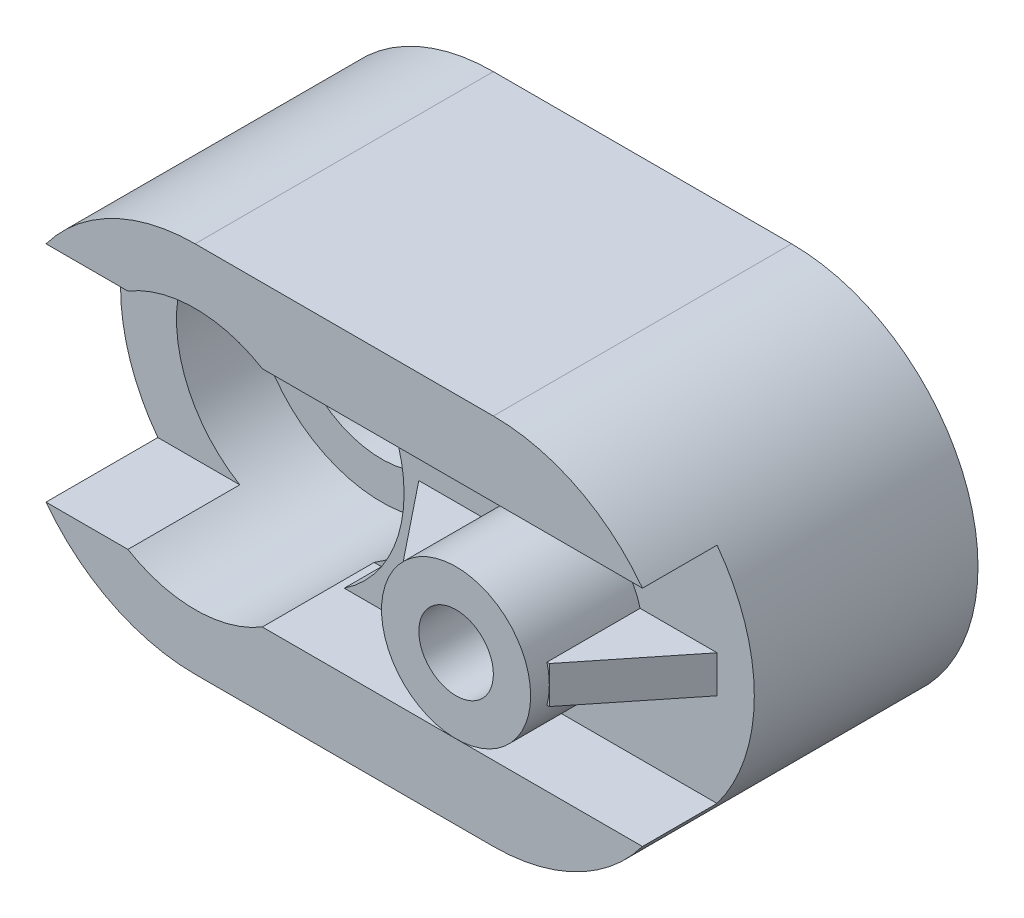
SolidWorks part; units mm, degrees
ref_plane "Front Plane" through (0, 0, 0) normal (0, 0, 1) x (1, 0, 0)
ref_plane "Top Plane" through (0, 0, 0) normal (0, 1, 0) x (1, 0, 0)
ref_plane "Right Plane" through (0, 0, 0) normal (1, 0, 0) x (0, 0, -1)
sketch "Sketch1" plane through (0, 0, 0) normal (0, 0, 1) x (1, 0, 0)
  line L1 (0, 0) -> (180, 0)
  line L2 (0, 0) -> (0, 100)
  line L3 (0, 100) -> (180, 100)
  line L4 (180, 0) -> (180, 100)
  arc A0 (50, 100) -> (50, 0) centre (50, 50) ccw
  arc A1 (130, 100) -> (130, 0) centre (130, 50) cw
  dimension "D7" = 50
  dimension "D10" = 50
  dimension "D1" = 180
  dimension "D2" = 100
  dimension "D3" = 50
  dimension "D4" = 50
  dimension "D5" = 50
  dimension "D6" = 50
  dimension "D8" = 50
  dimension "D9" = 50
extrude "Boss-Extrude1" add sketch "Sketch1" along normal blind 80 contours A1 L3 A0 L1 region at (90, 50, 0)
sketch "Sketch2" plane through (0, 0, 0) normal (1, 0, 0) x (0, 0, -1)
  line L0 (-80, 100) -> (-80, 0) construction
  line L1 (-80, 80) -> (-60, 80)
  line L2 (-80, 80) -> (-80, 70)
  line L3 (-80, 70) -> (-60, 70)
  line L4 (-60, 80) -> (-60, 70)
  line L5 (-80, 100) -> (0, 100) construction
  line L6 (-80, 0) -> (0, 0) construction
  line L7 (-80, 30) -> (-60, 30)
  line L8 (-80, 30) -> (-80, 20)
  line L9 (-80, 20) -> (-60, 20)
  line L10 (-60, 30) -> (-60, 20)
  dimension "D1" = 20
  dimension "D2" = 10
  dimension "D3" = 20
  dimension "D4" = 10
  dimension "D5" = 20
  dimension "D6" = 20
extrude "Cut-Extrude1" cut sketch "Sketch2" along normal blind 209
sketch "Sketch3" plane through (0, 0, 80) normal (0, 0, 1) x (1, 0, 0)
  line L0 (50, 0) -> (130, 0) construction
  circle A0 centre (130, 50) radius 10
  arc A1 (175.8258, 30) -> (175.8258, 70) centre (130, 50) ccw construction
  point P2 (180, 50)
  dimension "D1" = 20
  dimension "D2" = 50
  dimension "D3" = 50
extrude "Cut-Extrude2" cut sketch "Sketch3" against normal blind 40
sketch "Sketch4" plane through (0, 0, 80) normal (0, 0, 1) x (1, 0, 0)
  circle A0 centre (130, 50) radius 10
  circle A1 centre (130, 50) radius 20
  dimension "D1" = 20
  dimension "D2" = 40
extrude "Boss-Extrude2" add sketch "Sketch4" along normal blind 10
sketch "Sketch7" plane through (0, 0, 90) normal (0, 0, 1) x (1, 0, 0)
  point P0 (130, 50)
hole_wizard "Ø20.0mm Dowel Hole1" positions "3DSketch3" profile "Sketch8" hole size "Ø20.0" standard "ISO"
sketch3d "3DSketch3"
  point P0 (130, 50, 90)
sketch "Sketch8" plane through (130, 50, 90) normal (1, 0, 0) x (0, -1, 0)
  line L0 (0, 0) -> (0, 56.0086)
  line L1 (0, 56.0086) -> (10, 50)
  line L2 (10, 50) -> (10, 0)
  line L5 (10, 0) -> (0, 0)
  line L10 (0, 56.0086) -> (-10, 50) construction
  line L11 (0, -6.35) -> (0, 107.95) construction
  dimension "Hole Dia." = 20
  dimension "Hole Depth" = 50
  dimension "Drill Angle" = 118
sketch "Sketch9" plane through (0, 0, 80) normal (0, 0, 1) x (1, 0, 0)
  line L0 (4.1742, 30) -> (130, 30) construction
  line L1 (130, 70) -> (4.1742, 70)
  line L2 (130, 30) -> (4.1742, 30)
  arc A0 (130, 70) -> (130, 30) centre (130, 50) ccw
  arc A1 (4.1742, 70) -> (4.1742, 30) centre (50, 50) ccw
  arc A2 (4.1742, 70) -> (4.1742, 30) centre (50, 50) ccw construction
extrude "Cut-Extrude3" cut sketch "Sketch9" against normal blind 20
sketch "Sketch10" plane through (0, 0, 60) normal (0, 0, 1) x (1, 0, 0)
  line L0 (50, 0) -> (130, 0) construction
  circle A0 centre (50, 50) radius 10
  arc A1 (50, 100) -> (50, 0) centre (50, 50) ccw construction
  point P4 (0, 50)
  dimension "D1" = 20
  dimension "D2" = 50
  dimension "D3" = 50
extrude "Cut-Extrude4" cut sketch "Sketch10" against normal blind 74
sketch "Sketch11" plane through (0, 0, 60) normal (0, 0, 1) x (1, 0, 0)
  circle A0 centre (50, 50) radius 10
  circle A1 centre (50, 50) radius 25
  dimension "D1" = 20
  dimension "D2" = 50
extrude "Cut-Extrude5" cut sketch "Sketch11" against normal blind 40
sketch "Sketch12" plane through (0, 0, 60) normal (0, 0, 1) x (1, 0, 0)
  line L0 (170, 20) -> (10, 20) construction
  line L1 (10, 80) -> (70, 80)
  line L2 (170, 80) -> (10, 80) construction
  line L3 (10, 20) -> (70, 20)
  arc A0 (10, 80) -> (10, 20) centre (50, 50) ccw
  arc A1 (70, 80) -> (70, 20) centre (50, 50) cw
  circle M1 centre (50, 50) radius 25
  line M2 (170, 80) -> (10, 80)
  arc M3 (10, 80) -> (10, 20) centre (50, 50) ccw
  line M4 (10, 20) -> (170, 20)
  dimension "D1" = 60
  dimension "D2" = 60
extrude "Cut-Extrude6" cut sketch "Sketch12" against normal blind 10 contours A1 M2 M3 M4 M1 region at (40, 78.9509, 60)
sketch "Sketch14" plane through (0, 0, 60) normal (0, 0, 1) x (1, 0, 0)
  circle A0 centre (50, 50) radius 35
  circle A1 centre (50, 50) radius 25
  dimension "D1" = 70
  dimension "D2" = 50
extrude "Cut-Extrude7" cut sketch "Sketch14" against normal blind 30
sketch "Sketch15" plane through (0, 0, 80) normal (0, 0, 1) x (1, 0, 0)
  circle A0 centre (50, 50) radius 35
  dimension "D1" = 70
extrude "Cut-Extrude8" cut sketch "Sketch15" against normal blind 30
sketch "Sketch16" plane through (0, 0, 80) normal (0, 0, 1) x (1, 0, 0)
  line L0 (130, 70) -> (175.8258, 70)
  line L1 (130, 30) -> (175.8258, 30)
  arc A0 (130, 70) -> (130, 30) centre (130, 50) cw
  arc A1 (175.8258, 70) -> (175.8258, 30) centre (130, 50) cw
  arc A2 (175.8258, 30) -> (175.8258, 70) centre (130, 50) ccw construction
extrude "Cut-Extrude9" cut sketch "Sketch16" against normal blind 20
sketch "Sketch17" plane through (0, 0, 60) normal (0, 0, 1) x (1, 0, 0)
  line L1 (110, 50) -> (90, 50)
  line L2 (110, 50) -> (110, 45)
  line L3 (110, 45) -> (90, 45)
  line L4 (90, 50) -> (90, 45)
  line L5 (150, 50) -> (170, 50)
  line L6 (150, 50) -> (150, 45)
  line L7 (150, 45) -> (170, 45)
  line L8 (170, 50) -> (170, 45)
  line L9 (50, 0) -> (130, 0) construction
  line L10 (110, 45) -> (110.6351, 45)
  line L11 (150, 45) -> (149.3649, 45)
  circle A0 centre (130, 50) radius 20 construction
  arc A1 (110, 50) -> (110.6351, 45) centre (130, 50) ccw
  arc A2 (150, 50) -> (149.3649, 45) centre (130, 50) cw
  circle M1 centre (130, 50) radius 20
  dimension "D1" = 20
  dimension "D2" = 5
  dimension "D3" = 5
  dimension "D4" = 20
  dimension "D5" = 45
  dimension "D6" = 45
extrude "Boss-Extrude3" add sketch "Sketch17" along normal blind 25 contours L11 L6 M1 | L8 L5 L6 L7 | L2 L10 M1 | L1 L4 L3 L2 region at (100, 47.5, 60) region at (110.19, 46.246, 60) region at (160, 47.5, 60) region at (149.81, 46.246, 60)
sketch "Sketch18" plane through (0, 0, 85) normal (0, 0, 1) x (1, 0, 0)
  line L0 (110, 55) -> (110.6351, 55)
  line L1 (90, 50) -> (110, 50)
  line L2 (90, 50) -> (90, 55)
  line L3 (90, 55) -> (110, 55)
  line L4 (110, 50) -> (110, 55)
  circle A0 centre (130, 50) radius 20 construction
  arc A1 (110.6351, 55) -> (110, 50) centre (130, 50) ccw
  line M2 (110, 50) -> (90, 50)
  dimension "D1" = 5
  dimension "D2" = 20
extrude "Boss-Extrude4" add sketch "Sketch18" against normal blind 25 contours A1 L0 L4 | L4 L3 L2 M2 region at (100, 52.5, 85) region at (110.19, 53.754, 85)
sketch "Sketch19" plane through (0, 0, 85) normal (0, 0, 1) x (1, 0, 0)
  line L0 (150, 55) -> (149.3649, 55)
  line L1 (170, 50) -> (150, 50)
  line L2 (170, 50) -> (170, 55)
  line L3 (170, 55) -> (150, 55)
  line L4 (150, 50) -> (150, 55)
  circle A0 centre (130, 50) radius 20 construction
  arc A1 (149.3649, 55) -> (150, 50) centre (130, 50) cw
  line M3 (170, 50) -> (150, 50)
  dimension "D1" = 5
  dimension "D2" = 20
extrude "Boss-Extrude5" add sketch "Sketch19" against normal blind 25 contours L0 A1 L4 | L4 L2 L3 M3 region at (149.81, 53.754, 85) region at (160, 52.5, 85)
fillet "Chamfer1" radius 25 1 edges at (90, 50, 85) profile chamfer first distance on face at (90, 50, 72.5)
fillet "Chamfer3" radius 20 1 edges at (170, 50, 85) profile chamfer first distance on face at (159.8412, 50, 85)
